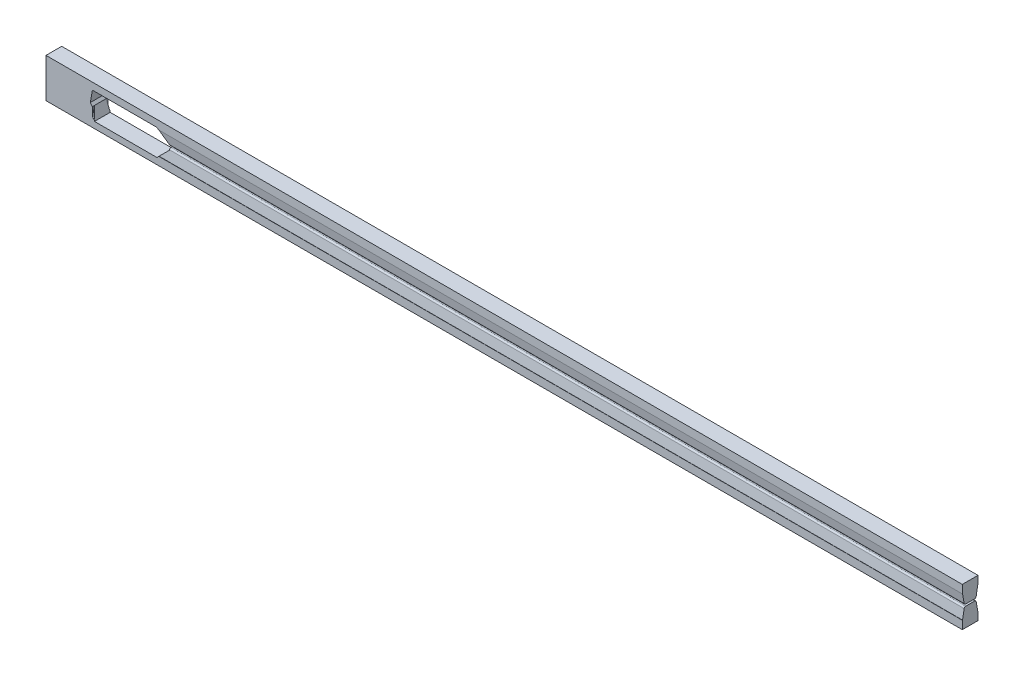
SolidWorks part; units mm, degrees
material "Purple Foam"
ref_plane "Front Plane" through (0, 0, 0) normal (0, 0, 1) x (1, 0, 0)
ref_plane "Top Plane" through (0, 0, 0) normal (0, 1, 0) x (1, 0, 0)
ref_plane "Right Plane" through (0, 0, 0) normal (1, 0, 0) x (0, 0, -1)
ref_axis "Axis1" through (0, -55, 0) along (0, 1, 0)
sketch "Sketch1" plane through (0, 0, 0) normal (1, 0, 0) x (0, 0, -1)
  line L0 (-101.1897, -204.724) -> (-86.7703, -204.724)
  line L1 (-101.1897, -204.724) -> (-86.7703, -204.724) construction
  line L2 (-86.5863, -208.788) -> (-101.3737, -208.788)
  line L3 (-86.5863, -208.788) -> (-101.3737, -208.788) construction
  line L4 (-93.98, -204.724) -> (-93.98, -174.498)
  line L6 (-214.4035, -174.498) -> (-223.2272, -174.498) construction
extrude "Extrude-Thin3" add sketch "Sketch1" along normal blind 664 and the other way blind 818 thin thin type mid plane wall 25.4
sketch "Sketch2" plane through (0, 0, 0) normal (1, 0, 0) x (0, 0, -1)
  line L0 (-167.5636, -192.1514) -> (-170.7101, -186.9072) construction
  line L1 (-176.3619, -185.674) -> (-172.8881, -185.674) construction
  line L2 (-178.5399, -186.9072) -> (-181.6864, -192.1514) construction
  line L3 (-145.9736, -192.1514) -> (-149.1201, -186.9072) construction
  line L4 (-154.7719, -185.674) -> (-151.2981, -185.674) construction
  line L5 (-156.9499, -186.9072) -> (-160.0964, -192.1514) construction
  line L6 (-124.3836, -192.1514) -> (-127.5301, -186.9072) construction
  line L7 (-133.1819, -185.674) -> (-129.7081, -185.674) construction
  line L8 (-135.3599, -186.9072) -> (-138.5064, -192.1514) construction
  line L9 (-117.602, -193.294) -> (-119.4865, -193.294) construction
  line L10 (-121.8135, -193.294) -> (-119.4865, -193.294) construction
  line L11 (-141.0765, -193.294) -> (-121.8135, -193.294) construction
  line L12 (-143.4035, -193.294) -> (-141.0765, -193.294) construction
  line L13 (-162.6665, -193.294) -> (-143.4035, -193.294) construction
  line L14 (-164.9935, -193.294) -> (-162.6665, -193.294) construction
  line L15 (-184.2565, -193.294) -> (-164.9935, -193.294) construction
  line L16 (-186.5835, -193.294) -> (-184.2565, -193.294) construction
  line L17 (-189.1536, -192.1514) -> (-192.3001, -186.9072) construction
  line L18 (-194.7187, -185.674) -> (-194.4781, -185.674) construction
  line L19 (-197.2201, -187.7729) -> (-198.1936, -193.294) construction
  line L20 (-167.5636, -192.1514) -> (-170.7101, -186.9072)
  line L21 (-176.3619, -185.674) -> (-172.8881, -185.674)
  line L22 (-178.5399, -186.9072) -> (-181.6864, -192.1514)
  line L23 (-145.9736, -192.1514) -> (-149.1201, -186.9072)
  line L24 (-154.7719, -185.674) -> (-151.2981, -185.674)
  line L25 (-156.9499, -186.9072) -> (-160.0964, -192.1514)
  line L26 (-124.3836, -192.1514) -> (-127.5301, -186.9072)
  line L27 (-133.1819, -185.674) -> (-129.7081, -185.674)
  line L28 (-135.3599, -186.9072) -> (-138.5064, -192.1514)
  line L29 (-117.602, -193.294) -> (-119.4865, -193.294)
  line L30 (-121.8135, -193.294) -> (-119.4865, -193.294)
  line L31 (-141.0765, -193.294) -> (-121.8135, -193.294)
  line L32 (-143.4035, -193.294) -> (-141.0765, -193.294)
  line L33 (-162.6665, -193.294) -> (-143.4035, -193.294)
  line L34 (-164.9935, -193.294) -> (-162.6665, -193.294)
  line L35 (-184.2565, -193.294) -> (-164.9935, -193.294)
  line L36 (-186.5835, -193.294) -> (-184.2565, -193.294)
  line L37 (-189.1536, -192.1514) -> (-192.3001, -186.9072)
  line L38 (-194.7187, -185.674) -> (-194.4781, -185.674)
  line L39 (-197.2201, -187.7729) -> (-198.1936, -193.294)
  line L40 (-34.5669, -192.0601) -> (-37.0202, -187.0898) construction
  line L41 (-56.1418, -193.294) -> (-58.0878, -193.294) construction
  line L42 (-56.1418, -193.294) -> (-47.9982, -193.294) construction
  line L43 (-42.9898, -187.0898) -> (-45.4431, -192.0601) construction
  line L44 (-40.7122, -185.674) -> (-39.2978, -185.674) construction
  line L45 (-10.4369, -192.0601) -> (-12.8902, -187.0898) construction
  line L46 (-16.5822, -185.674) -> (-15.1678, -185.674) construction
  line L47 (-18.8598, -187.0898) -> (-21.3131, -192.0601) construction
  line L48 (13.6931, -192.0601) -> (11.2398, -187.0898) construction
  line L49 (7.5478, -185.674) -> (8.9622, -185.674) construction
  line L50 (5.2702, -187.0898) -> (2.8169, -192.0601) construction
  line L51 (37.8231, -192.0601) -> (35.3698, -187.0898) construction
  line L52 (31.6778, -185.674) -> (33.0922, -185.674) construction
  line L53 (29.4002, -187.0898) -> (26.9469, -192.0601) construction
  line L54 (61.9531, -192.0601) -> (59.4998, -187.0898) construction
  line L55 (55.8078, -185.674) -> (57.2222, -185.674) construction
  line L56 (53.5302, -187.0898) -> (51.0769, -192.0601) construction
  line L57 (86.0831, -192.0601) -> (83.6298, -187.0898) construction
  line L58 (79.9378, -185.674) -> (81.3522, -185.674) construction
  line L59 (77.6602, -187.0898) -> (75.2069, -192.0601) construction
  line L60 (110.2131, -192.0601) -> (107.7598, -187.0898) construction
  line L61 (104.0678, -185.674) -> (105.4822, -185.674) construction
  line L62 (101.7902, -187.0898) -> (99.3369, -192.0601) construction
  line L63 (134.3431, -192.0601) -> (131.8898, -187.0898) construction
  line L64 (128.1978, -185.674) -> (129.6122, -185.674) construction
  line L65 (125.9202, -187.0898) -> (123.4669, -192.0601) construction
  line L66 (158.4731, -192.0601) -> (156.0198, -187.0898) construction
  line L67 (152.3278, -185.674) -> (153.7422, -185.674) construction
  line L68 (150.0502, -187.0898) -> (147.5969, -192.0601) construction
  line L69 (198.1936, -193.294) -> (197.2201, -187.7729) construction
  line L70 (176.4578, -185.674) -> (194.7187, -185.674) construction
  line L71 (174.1802, -187.0898) -> (171.7269, -192.0601) construction
  line L72 (169.1718, -193.294) -> (198.1936, -193.294) construction
  line L73 (161.0282, -193.294) -> (169.1718, -193.294) construction
  line L74 (145.0418, -193.294) -> (161.0282, -193.294) construction
  line L75 (136.8982, -193.294) -> (145.0418, -193.294) construction
  line L76 (120.9118, -193.294) -> (136.8982, -193.294) construction
  line L77 (112.7682, -193.294) -> (120.9118, -193.294) construction
  line L78 (96.7818, -193.294) -> (112.7682, -193.294) construction
  line L79 (88.6382, -193.294) -> (96.7818, -193.294) construction
  line L80 (72.6518, -193.294) -> (88.6382, -193.294) construction
  line L81 (64.5082, -193.294) -> (72.6518, -193.294) construction
  line L82 (48.5218, -193.294) -> (64.5082, -193.294) construction
  line L83 (40.3782, -193.294) -> (48.5218, -193.294) construction
  line L84 (24.3918, -193.294) -> (40.3782, -193.294) construction
  line L85 (16.2482, -193.294) -> (24.3918, -193.294) construction
  line L86 (0.2618, -193.294) -> (16.2482, -193.294) construction
  line L87 (-7.8818, -193.294) -> (0.2618, -193.294) construction
  line L88 (-23.8682, -193.294) -> (-7.8818, -193.294) construction
  line L89 (-32.0118, -193.294) -> (-23.8682, -193.294) construction
  line L90 (-56.1418, -193.294) -> (-58.0878, -193.294)
  line L91 (-56.1418, -193.294) -> (-47.9982, -193.294)
  line L92 (-42.9898, -187.0898) -> (-45.4431, -192.0601)
  line L93 (-40.7122, -185.674) -> (-39.2978, -185.674)
  line L94 (-10.4369, -192.0601) -> (-12.8902, -187.0898)
  line L95 (-16.5822, -185.674) -> (-15.1678, -185.674)
  line L96 (-18.8598, -187.0898) -> (-21.3131, -192.0601)
  line L97 (13.6931, -192.0601) -> (11.2398, -187.0898)
  line L98 (7.5478, -185.674) -> (8.9622, -185.674)
  line L99 (5.2702, -187.0898) -> (2.8169, -192.0601)
  line L100 (37.8231, -192.0601) -> (35.3698, -187.0898)
  line L101 (31.6778, -185.674) -> (33.0922, -185.674)
  line L102 (29.4002, -187.0898) -> (26.9469, -192.0601)
  line L103 (61.9531, -192.0601) -> (59.4998, -187.0898)
  line L104 (55.8078, -185.674) -> (57.2222, -185.674)
  line L105 (53.5302, -187.0898) -> (51.0769, -192.0601)
  line L106 (86.0831, -192.0601) -> (83.6298, -187.0898)
  line L107 (79.9378, -185.674) -> (81.3522, -185.674)
  line L108 (77.6602, -187.0898) -> (75.2069, -192.0601)
  line L109 (110.2131, -192.0601) -> (107.7598, -187.0898)
  line L110 (104.0678, -185.674) -> (105.4822, -185.674)
  line L111 (101.7902, -187.0898) -> (99.3369, -192.0601)
  line L112 (134.3431, -192.0601) -> (131.8898, -187.0898)
  line L113 (128.1978, -185.674) -> (129.6122, -185.674)
  line L114 (125.9202, -187.0898) -> (123.4669, -192.0601)
  line L115 (158.4731, -192.0601) -> (156.0198, -187.0898)
  line L116 (152.3278, -185.674) -> (153.7422, -185.674)
  line L117 (150.0502, -187.0898) -> (147.5969, -192.0601)
  line L118 (198.1936, -193.294) -> (197.2201, -187.7729)
  line L119 (176.4578, -185.674) -> (194.7187, -185.674)
  line L120 (174.1802, -187.0898) -> (171.7269, -192.0601)
  line L121 (169.1718, -193.294) -> (198.1936, -193.294)
  line L122 (161.0282, -193.294) -> (169.1718, -193.294)
  line L123 (145.0418, -193.294) -> (161.0282, -193.294)
  line L124 (136.8982, -193.294) -> (145.0418, -193.294)
  line L125 (120.9118, -193.294) -> (136.8982, -193.294)
  line L126 (112.7682, -193.294) -> (120.9118, -193.294)
  line L127 (96.7818, -193.294) -> (112.7682, -193.294)
  line L128 (88.6382, -193.294) -> (96.7818, -193.294)
  line L129 (72.6518, -193.294) -> (88.6382, -193.294)
  line L130 (64.5082, -193.294) -> (72.6518, -193.294)
  line L131 (48.5218, -193.294) -> (64.5082, -193.294)
  line L132 (40.3782, -193.294) -> (48.5218, -193.294)
  line L133 (24.3918, -193.294) -> (40.3782, -193.294)
  line L134 (16.2482, -193.294) -> (24.3918, -193.294)
  line L135 (0.2618, -193.294) -> (16.2482, -193.294)
  line L136 (-7.8818, -193.294) -> (0.2618, -193.294)
  line L137 (-23.8682, -193.294) -> (-7.8818, -193.294)
  line L138 (-32.0118, -193.294) -> (-23.8682, -193.294)
  line L139 (-34.5669, -192.0601) -> (-37.0202, -187.0898)
  arc A0 (-170.7101, -186.9072) -> (-172.8881, -185.674) centre (-172.8881, -188.214) ccw construction
  arc A1 (-176.3619, -185.674) -> (-178.5399, -186.9072) centre (-176.3619, -188.214) ccw construction
  arc A2 (-149.1201, -186.9072) -> (-151.2981, -185.674) centre (-151.2981, -188.214) ccw construction
  arc A3 (-154.7719, -185.674) -> (-156.9499, -186.9072) centre (-154.7719, -188.214) ccw construction
  arc A4 (-127.5301, -186.9072) -> (-129.7081, -185.674) centre (-129.7081, -188.214) ccw construction
  arc A5 (-133.1819, -185.674) -> (-135.3599, -186.9072) centre (-133.1819, -188.214) ccw construction
  arc A6 (-192.3001, -186.9072) -> (-194.4781, -185.674) centre (-194.4781, -188.214) ccw construction
  arc A7 (-194.7187, -185.674) -> (-197.2201, -187.7729) centre (-194.7187, -188.214) ccw construction
  arc A8 (-170.7101, -186.9072) -> (-172.8881, -185.674) centre (-172.8881, -188.214) ccw
  arc A9 (-176.3619, -185.674) -> (-178.5399, -186.9072) centre (-176.3619, -188.214) ccw
  arc A10 (-149.1201, -186.9072) -> (-151.2981, -185.674) centre (-151.2981, -188.214) ccw
  arc A11 (-154.7719, -185.674) -> (-156.9499, -186.9072) centre (-154.7719, -188.214) ccw
  arc A12 (-127.5301, -186.9072) -> (-129.7081, -185.674) centre (-129.7081, -188.214) ccw
  arc A13 (-133.1819, -185.674) -> (-135.3599, -186.9072) centre (-133.1819, -188.214) ccw
  arc A14 (-192.3001, -186.9072) -> (-194.4781, -185.674) centre (-194.4781, -188.214) ccw
  arc A15 (-194.7187, -185.674) -> (-197.2201, -187.7729) centre (-194.7187, -188.214) ccw
  arc A16 (-40.7122, -185.674) -> (-42.9898, -187.0898) centre (-40.7122, -188.214) ccw construction
  arc A17 (-37.0202, -187.0898) -> (-39.2978, -185.674) centre (-39.2978, -188.214) ccw construction
  arc A18 (-12.8902, -187.0898) -> (-15.1678, -185.674) centre (-15.1678, -188.214) ccw construction
  arc A19 (-16.5822, -185.674) -> (-18.8598, -187.0898) centre (-16.5822, -188.214) ccw construction
  arc A20 (11.2398, -187.0898) -> (8.9622, -185.674) centre (8.9622, -188.214) ccw construction
  arc A21 (7.5478, -185.674) -> (5.2702, -187.0898) centre (7.5478, -188.214) ccw construction
  arc A22 (35.3698, -187.0898) -> (33.0922, -185.674) centre (33.0922, -188.214) ccw construction
  arc A23 (31.6778, -185.674) -> (29.4002, -187.0898) centre (31.6778, -188.214) ccw construction
  arc A24 (59.4998, -187.0898) -> (57.2222, -185.674) centre (57.2222, -188.214) ccw construction
  arc A25 (55.8078, -185.674) -> (53.5302, -187.0898) centre (55.8078, -188.214) ccw construction
  arc A26 (83.6298, -187.0898) -> (81.3522, -185.674) centre (81.3522, -188.214) ccw construction
  arc A27 (79.9378, -185.674) -> (77.6602, -187.0898) centre (79.9378, -188.214) ccw construction
  arc A28 (107.7598, -187.0898) -> (105.4822, -185.674) centre (105.4822, -188.214) ccw construction
  arc A29 (104.0678, -185.674) -> (101.7902, -187.0898) centre (104.0678, -188.214) ccw construction
  arc A30 (131.8898, -187.0898) -> (129.6122, -185.674) centre (129.6122, -188.214) ccw construction
  arc A31 (128.1978, -185.674) -> (125.9202, -187.0898) centre (128.1978, -188.214) ccw construction
  arc A32 (156.0198, -187.0898) -> (153.7422, -185.674) centre (153.7422, -188.214) ccw construction
  arc A33 (152.3278, -185.674) -> (150.0502, -187.0898) centre (152.3278, -188.214) ccw construction
  arc A34 (197.2201, -187.7729) -> (194.7187, -185.674) centre (194.7187, -188.214) ccw construction
  arc A35 (176.4578, -185.674) -> (174.1802, -187.0898) centre (176.4578, -188.214) ccw construction
  arc A36 (-40.7122, -185.674) -> (-42.9898, -187.0898) centre (-40.7122, -188.214) ccw
  arc A37 (-37.0202, -187.0898) -> (-39.2978, -185.674) centre (-39.2978, -188.214) ccw
  arc A38 (-12.8902, -187.0898) -> (-15.1678, -185.674) centre (-15.1678, -188.214) ccw
  arc A39 (-16.5822, -185.674) -> (-18.8598, -187.0898) centre (-16.5822, -188.214) ccw
  arc A40 (11.2398, -187.0898) -> (8.9622, -185.674) centre (8.9622, -188.214) ccw
  arc A41 (7.5478, -185.674) -> (5.2702, -187.0898) centre (7.5478, -188.214) ccw
  arc A42 (35.3698, -187.0898) -> (33.0922, -185.674) centre (33.0922, -188.214) ccw
  arc A43 (31.6778, -185.674) -> (29.4002, -187.0898) centre (31.6778, -188.214) ccw
  arc A44 (59.4998, -187.0898) -> (57.2222, -185.674) centre (57.2222, -188.214) ccw
  arc A45 (55.8078, -185.674) -> (53.5302, -187.0898) centre (55.8078, -188.214) ccw
  arc A46 (83.6298, -187.0898) -> (81.3522, -185.674) centre (81.3522, -188.214) ccw
  arc A47 (79.9378, -185.674) -> (77.6602, -187.0898) centre (79.9378, -188.214) ccw
  arc A48 (107.7598, -187.0898) -> (105.4822, -185.674) centre (105.4822, -188.214) ccw
  arc A49 (104.0678, -185.674) -> (101.7902, -187.0898) centre (104.0678, -188.214) ccw
  arc A50 (131.8898, -187.0898) -> (129.6122, -185.674) centre (129.6122, -188.214) ccw
  arc A51 (128.1978, -185.674) -> (125.9202, -187.0898) centre (128.1978, -188.214) ccw
  arc A52 (156.0198, -187.0898) -> (153.7422, -185.674) centre (153.7422, -188.214) ccw
  arc A53 (152.3278, -185.674) -> (150.0502, -187.0898) centre (152.3278, -188.214) ccw
  arc A54 (197.2201, -187.7729) -> (194.7187, -185.674) centre (194.7187, -188.214) ccw
  arc A55 (176.4578, -185.674) -> (174.1802, -187.0898) centre (176.4578, -188.214) ccw
  ellipse E0 centre (-164.9935, -191.4979) end of major axis (-167.7527, -191.4979) minor radius 1.7961 (-167.5636, -192.1514) -> (-164.9935, -193.294) ccw construction
  ellipse E1 centre (-184.2565, -191.4979) end of major axis (-187.0156, -191.4979) minor radius 1.7961 (-184.2565, -193.294) -> (-181.6864, -192.1514) ccw construction
  ellipse E2 centre (-143.4035, -191.4979) end of major axis (-146.1627, -191.4979) minor radius 1.7961 (-145.9736, -192.1514) -> (-143.4035, -193.294) ccw construction
  ellipse E3 centre (-162.6665, -191.4979) end of major axis (-165.4256, -191.4979) minor radius 1.7961 (-162.6665, -193.294) -> (-160.0964, -192.1514) ccw construction
  ellipse E4 centre (-121.8135, -191.4979) end of major axis (-124.5727, -191.4979) minor radius 1.7961 (-124.3836, -192.1514) -> (-121.8135, -193.294) ccw construction
  ellipse E5 centre (-141.0765, -191.4979) end of major axis (-143.8356, -191.4979) minor radius 1.7961 (-141.0765, -193.294) -> (-138.5064, -192.1514) ccw construction
  ellipse E6 centre (-186.5835, -191.4979) end of major axis (-189.3427, -191.4979) minor radius 1.7961 (-189.1536, -192.1514) -> (-186.5835, -193.294) ccw construction
  ellipse E7 centre (-164.9935, -191.4979) end of major axis (-167.7527, -191.4979) minor radius 1.7961 (-167.5636, -192.1514) -> (-164.9935, -193.294) ccw
  ellipse E8 centre (-184.2565, -191.4979) end of major axis (-187.0156, -191.4979) minor radius 1.7961 (-184.2565, -193.294) -> (-181.6864, -192.1514) ccw
  ellipse E9 centre (-143.4035, -191.4979) end of major axis (-146.1627, -191.4979) minor radius 1.7961 (-145.9736, -192.1514) -> (-143.4035, -193.294) ccw
  ellipse E10 centre (-162.6665, -191.4979) end of major axis (-165.4256, -191.4979) minor radius 1.7961 (-162.6665, -193.294) -> (-160.0964, -192.1514) ccw
  ellipse E11 centre (-121.8135, -191.4979) end of major axis (-124.5727, -191.4979) minor radius 1.7961 (-124.3836, -192.1514) -> (-121.8135, -193.294) ccw
  ellipse E12 centre (-141.0765, -191.4979) end of major axis (-143.8356, -191.4979) minor radius 1.7961 (-141.0765, -193.294) -> (-138.5064, -192.1514) ccw
  ellipse E13 centre (-186.5835, -191.4979) end of major axis (-189.3427, -191.4979) minor radius 1.7961 (-189.1536, -192.1514) -> (-186.5835, -193.294) ccw
  ellipse E14 centre (-47.9982, -191.4979) end of major axis (-50.6885, -191.4979) minor radius 1.7961 (-47.9982, -193.294) -> (-45.4431, -192.0601) ccw construction
  ellipse E15 centre (-7.8818, -191.4979) end of major axis (-10.5721, -191.4979) minor radius 1.7961 (-10.4369, -192.0601) -> (-7.8818, -193.294) ccw construction
  ellipse E16 centre (-23.8682, -191.4979) end of major axis (-26.5585, -191.4979) minor radius 1.7961 (-23.8682, -193.294) -> (-21.3131, -192.0601) ccw construction
  ellipse E17 centre (16.2482, -191.4979) end of major axis (13.5579, -191.4979) minor radius 1.7961 (13.6931, -192.0601) -> (16.2482, -193.294) ccw construction
  ellipse E18 centre (0.2618, -191.4979) end of major axis (-2.4285, -191.4979) minor radius 1.7961 (0.2618, -193.294) -> (2.8169, -192.0601) ccw construction
  ellipse E19 centre (40.3782, -191.4979) end of major axis (37.6879, -191.4979) minor radius 1.7961 (37.8231, -192.0601) -> (40.3782, -193.294) ccw construction
  ellipse E20 centre (24.3918, -191.4979) end of major axis (21.7015, -191.4979) minor radius 1.7961 (24.3918, -193.294) -> (26.9469, -192.0601) ccw construction
  ellipse E21 centre (64.5082, -191.4979) end of major axis (61.8179, -191.4979) minor radius 1.7961 (61.9531, -192.0601) -> (64.5082, -193.294) ccw construction
  ellipse E22 centre (48.5218, -191.4979) end of major axis (45.8315, -191.4979) minor radius 1.7961 (48.5218, -193.294) -> (51.0769, -192.0601) ccw construction
  ellipse E23 centre (88.6382, -191.4979) end of major axis (85.9479, -191.4979) minor radius 1.7961 (86.0831, -192.0601) -> (88.6382, -193.294) ccw construction
  ellipse E24 centre (72.6518, -191.4979) end of major axis (69.9615, -191.4979) minor radius 1.7961 (72.6518, -193.294) -> (75.2069, -192.0601) ccw construction
  ellipse E25 centre (112.7682, -191.4979) end of major axis (110.0779, -191.4979) minor radius 1.7961 (110.2131, -192.0601) -> (112.7682, -193.294) ccw construction
  ellipse E26 centre (96.7818, -191.4979) end of major axis (94.0915, -191.4979) minor radius 1.7961 (96.7818, -193.294) -> (99.3369, -192.0601) ccw construction
  ellipse E27 centre (136.8982, -191.4979) end of major axis (134.2079, -191.4979) minor radius 1.7961 (134.3431, -192.0601) -> (136.8982, -193.294) ccw construction
  ellipse E28 centre (120.9118, -191.4979) end of major axis (118.2215, -191.4979) minor radius 1.7961 (120.9118, -193.294) -> (123.4669, -192.0601) ccw construction
  ellipse E29 centre (161.0282, -191.4979) end of major axis (158.3379, -191.4979) minor radius 1.7961 (158.4731, -192.0601) -> (161.0282, -193.294) ccw construction
  ellipse E30 centre (145.0418, -191.4979) end of major axis (142.3515, -191.4979) minor radius 1.7961 (145.0418, -193.294) -> (147.5969, -192.0601) ccw construction
  ellipse E31 centre (169.1718, -191.4979) end of major axis (166.4815, -191.4979) minor radius 1.7961 (169.1718, -193.294) -> (171.7269, -192.0601) ccw construction
  ellipse E32 centre (-32.0118, -191.4979) end of major axis (-34.7021, -191.4979) minor radius 1.7961 (-34.5669, -192.0601) -> (-32.0118, -193.294) ccw construction
  ellipse E33 centre (-47.9982, -191.4979) end of major axis (-50.6885, -191.4979) minor radius 1.7961 (-47.9982, -193.294) -> (-45.4431, -192.0601) ccw
  ellipse E34 centre (-7.8818, -191.4979) end of major axis (-10.5721, -191.4979) minor radius 1.7961 (-10.4369, -192.0601) -> (-7.8818, -193.294) ccw
  ellipse E35 centre (-23.8682, -191.4979) end of major axis (-26.5585, -191.4979) minor radius 1.7961 (-23.8682, -193.294) -> (-21.3131, -192.0601) ccw
  ellipse E36 centre (16.2482, -191.4979) end of major axis (13.5579, -191.4979) minor radius 1.7961 (13.6931, -192.0601) -> (16.2482, -193.294) ccw
  ellipse E37 centre (0.2618, -191.4979) end of major axis (-2.4285, -191.4979) minor radius 1.7961 (0.2618, -193.294) -> (2.8169, -192.0601) ccw
  ellipse E38 centre (40.3782, -191.4979) end of major axis (37.6879, -191.4979) minor radius 1.7961 (37.8231, -192.0601) -> (40.3782, -193.294) ccw
  ellipse E39 centre (24.3918, -191.4979) end of major axis (21.7015, -191.4979) minor radius 1.7961 (24.3918, -193.294) -> (26.9469, -192.0601) ccw
  ellipse E40 centre (64.5082, -191.4979) end of major axis (61.8179, -191.4979) minor radius 1.7961 (61.9531, -192.0601) -> (64.5082, -193.294) ccw
  ellipse E41 centre (48.5218, -191.4979) end of major axis (45.8315, -191.4979) minor radius 1.7961 (48.5218, -193.294) -> (51.0769, -192.0601) ccw
  ellipse E42 centre (88.6382, -191.4979) end of major axis (85.9479, -191.4979) minor radius 1.7961 (86.0831, -192.0601) -> (88.6382, -193.294) ccw
  ellipse E43 centre (72.6518, -191.4979) end of major axis (69.9615, -191.4979) minor radius 1.7961 (72.6518, -193.294) -> (75.2069, -192.0601) ccw
  ellipse E44 centre (112.7682, -191.4979) end of major axis (110.0779, -191.4979) minor radius 1.7961 (110.2131, -192.0601) -> (112.7682, -193.294) ccw
  ellipse E45 centre (96.7818, -191.4979) end of major axis (94.0915, -191.4979) minor radius 1.7961 (96.7818, -193.294) -> (99.3369, -192.0601) ccw
  ellipse E46 centre (136.8982, -191.4979) end of major axis (134.2079, -191.4979) minor radius 1.7961 (134.3431, -192.0601) -> (136.8982, -193.294) ccw
  ellipse E47 centre (120.9118, -191.4979) end of major axis (118.2215, -191.4979) minor radius 1.7961 (120.9118, -193.294) -> (123.4669, -192.0601) ccw
  ellipse E48 centre (161.0282, -191.4979) end of major axis (158.3379, -191.4979) minor radius 1.7961 (158.4731, -192.0601) -> (161.0282, -193.294) ccw
  ellipse E49 centre (145.0418, -191.4979) end of major axis (142.3515, -191.4979) minor radius 1.7961 (145.0418, -193.294) -> (147.5969, -192.0601) ccw
  ellipse E50 centre (169.1718, -191.4979) end of major axis (166.4815, -191.4979) minor radius 1.7961 (169.1718, -193.294) -> (171.7269, -192.0601) ccw
  ellipse E51 centre (-32.0118, -191.4979) end of major axis (-34.7021, -191.4979) minor radius 1.7961 (-34.5669, -192.0601) -> (-32.0118, -193.294) ccw
sketch "Sketch3" plane through (0, 0, 0) normal (1, 0, 0) x (0, 0, -1)
  line L0 (-81.6501, -187.7729) -> (-84.2689, -202.6251) construction
  line L1 (-103.6911, -202.6251) -> (-106.3099, -187.7729) construction
  line L2 (-81.6501, -187.7729) -> (-84.2689, -202.6251)
  line L3 (-103.6911, -202.6251) -> (-106.3099, -187.7729)
  line L4 (-101.1897, -204.724) -> (-86.7703, -204.724)
  line L5 (-106.3099, -187.7729) -> (-112.0906, -187.7729)
  line L6 (-112.0906, -187.7729) -> (-112.0906, -212.1682)
  line L7 (-112.0906, -212.1682) -> (-76.5462, -212.1682)
  line L8 (-76.5462, -212.1682) -> (-76.5462, -187.7729)
  line L9 (-76.5462, -187.7729) -> (-81.6501, -187.7729)
  arc A0 (-86.7703, -204.724) -> (-84.2689, -202.6251) centre (-86.7703, -202.184) ccw construction
  arc A1 (-103.6911, -202.6251) -> (-101.1897, -204.724) centre (-101.1897, -202.184) ccw construction
  arc A2 (-86.7703, -204.724) -> (-84.2689, -202.6251) centre (-86.7703, -202.184) ccw
  arc A3 (-103.6911, -202.6251) -> (-101.1897, -204.724) centre (-101.1897, -202.184) ccw
extrude "Cut-Extrude1" cut sketch "Sketch3" against normal blind 743 and the other way blind 674
ref_plane "Plane1" through (0, -206.248, 0) normal (0, 1, 0) x (1, 0, 0)
mirror "Mirror3" about plane through (0, -206.248, 0) normal (0, 1, 0) of bodies 103
sketch "Sketch4" plane through (0, -207.772, 0) normal (0, 1, 0) x (1, 0, 0)
  line L1 (-818, -81.28) -> (-818, -106.68) construction
  line L2 (-818, -81.28) -> (-743, -81.28) construction
  line L3 (-818, -106.68) -> (-738, -106.68)
  line L4 (-818, -81.28) -> (-818, -106.68)
  line L5 (-818, -81.28) -> (-738, -81.28)
  line L6 (-738, -81.28) -> (-738, -106.68)
  dimension "D1" = 80
  dimension "D2" = 25.4
extrude "Boss-Extrude1" add sketch "Sketch4" along normal up to surface (3.048 mm away) up to face at (-410, -204.724, 93.98)
sketch "Sketch6" plane through (0, 0, 0) normal (0, 0, 1) x (1, 0, 0)
  line L0 (665.48, -185.674) -> (-742.95, -185.674) construction
  line L1 (-638.4636, -185.674) -> (-742.95, -185.674)
  line L2 (-744.2936, -193.294) -> (-746.309, -204.724) construction
  line L3 (-744.2936, -193.294) -> (-746.309, -204.724)
  line L4 (-744.2936, -193.294) -> (-743.1996, -187.0898) construction
  line L5 (-744.2936, -193.294) -> (-742.95, -185.674)
  line L6 (-636.1, -188.0376) -> (-621.2479, -202.8897) construction
  line L7 (-638.4636, -185.674) -> (-621.2479, -202.8897)
  line L8 (-621.2479, -210.4459) -> (-634.0011, -223.1991) construction
  line L9 (-621.2479, -210.4459) -> (-638.64, -227.838)
  line L10 (-739.591, -227.838) -> (749.3, -227.838) construction
  line L11 (-739.591, -227.838) -> (-638.64, -227.838)
  line L12 (-739.8446, -226.3995) -> (-740.9346, -220.218) construction
  line L13 (-739.591, -227.838) -> (-740.9346, -220.218)
  line L14 (-742.95, -208.788) -> (-740.9346, -220.218) construction
  line L15 (-742.95, -208.788) -> (-740.9346, -220.218)
  line L16 (-742.95, -208.788) -> (-746.309, -204.724)
  line L17 (-621.2479, -202.8897) -> (-621.2479, -210.4459)
extrude "Cut-Extrude2" cut sketch "Sketch6" along normal blind 178
